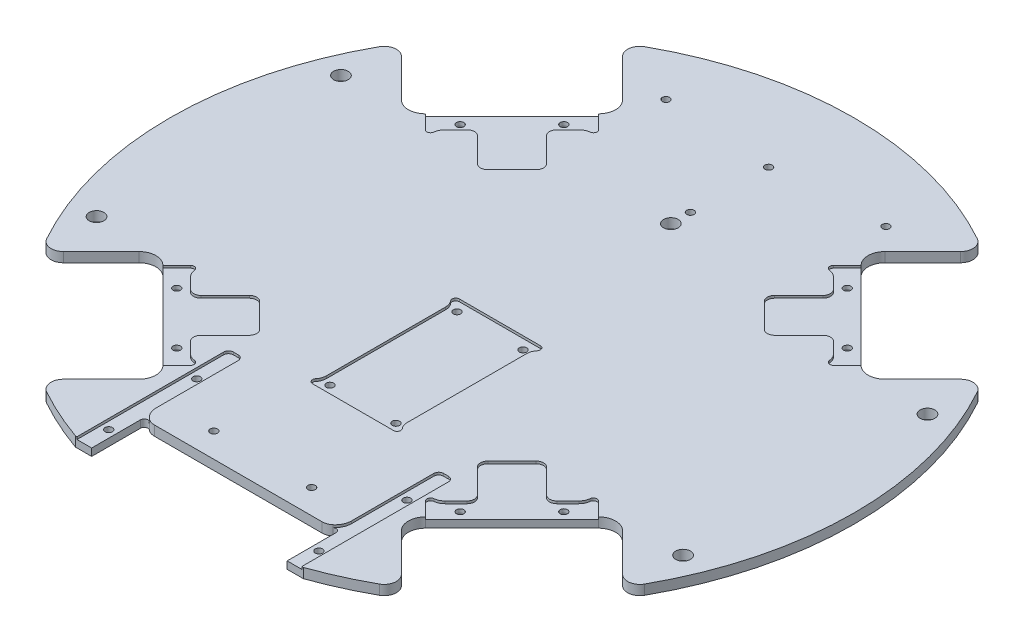
SolidWorks part; units mm, degrees
material "ABS PC"
ref_plane "Front Plane" through (0, 0, 0) normal (0, 0, 1) x (1, 0, 0)
ref_plane "Top Plane" through (0, 0, 0) normal (0, 1, 0) x (1, 0, 0)
ref_plane "Right Plane" through (0, 0, 0) normal (1, 0, 0) x (0, 0, -1)
sketch "Sketch1" plane through (0, 0, 0) normal (0, 1, 0) x (1, 0, 0)
  circle A0 centre (0, 0) radius 140
  dimension "D1" = 280
extrude "Boss-Extrude1" add sketch "Sketch1" along normal blind 4
sketch "Sketch7" plane through (0, 4, 0) normal (0, 1, 0) x (1, 0, 0)
  line L0 (-89.1308, -53.7048) -> (-53.7048, -89.1308)
  line L1 (-98.9596, -53.7048) -> (-121.6224, -76.3675)
  line L2 (-53.7048, -98.9596) -> (-76.3675, -121.6224)
  line L3 (-121.6224, -76.3675) -> (-76.3675, -121.6224)
  line L4 (0, 0) -> (-98.9949, -98.9949) construction
  line L7 (0, 0) -> (0, 130) construction
  circle A0 centre (0, 0) radius 140 construction
  arc A1 (-98.9596, -53.7048) -> (-89.1308, -53.7048) centre (-94.0452, -58.6192) cw
  arc A2 (-53.7048, -89.1308) -> (-53.7048, -98.9596) centre (-58.6192, -94.0452) cw
  dimension "D4" = 6.95
  dimension "D1" = 101
  dimension "D2" = 64
  dimension "D3" = 135
extrude "Cut-Extrude4" cut sketch "Sketch7" against normal up to next
sketch "Sketch8" plane through (0, 4, 0) normal (0, 1, 0) x (1, 0, 0)
  line L0 (-89.1308, -53.7048) -> (-53.7048, -89.1308)
  line L1 (-89.1308, -53.7048) -> (-83.474, -48.0479)
  line L2 (-53.7048, -89.1308) -> (-48.0479, -83.474)
  line L3 (-79.4765, -52.0454) -> (-52.0454, -79.4765)
  line L6 (-53.7048, -89.1308) -> (-89.1308, -53.7048) construction
  arc A0 (-83.474, -48.0479) -> (-80.9197, -48.9704) centre (-82.4133, -49.1086) cw
  arc A1 (-80.9197, -48.9704) -> (-79.4765, -52.0454) centre (-75.9409, -48.5099) ccw
  arc A2 (-48.0479, -83.474) -> (-48.9704, -80.9197) centre (-49.1086, -82.4133) ccw
  arc A3 (-48.9704, -80.9197) -> (-52.0454, -79.4765) centre (-48.5099, -75.9409) cw
  dimension "D2" = 1.5
  dimension "D3" = 5
  dimension "D4" = 1.5
  dimension "D5" = 5
  dimension "D1" = 8
extrude "Cut-Extrude5" cut sketch "Sketch8" against normal blind 1
sketch "Sketch14" plane through (0, 4, 0) normal (0, 1, 0) x (1, 0, 0)
  line L0 (-52.0454, -79.4765) -> (-79.4765, -52.0454) construction
  line L1 (-52.0454, -79.4765) -> (-79.4765, -52.0454) construction
  line L2 (-70.7107, -56.5685) -> (-60.8112, -46.669)
  line L3 (-56.5685, -70.7107) -> (-46.669, -60.8112)
  line L4 (-56.5685, -46.669) -> (-46.669, -56.5685)
  line L5 (-74.9533, -56.5685) -> (-56.5685, -74.9533)
  line L8 (-83.474, -48.0479) -> (-89.1308, -53.7048) construction
  arc A0 (-74.9533, -56.5685) -> (-70.7107, -56.5685) centre (-72.832, -54.4472) ccw
  arc A1 (-56.5685, -74.9533) -> (-56.5685, -70.7107) centre (-54.4472, -72.832) cw
  arc A2 (-60.8112, -46.669) -> (-56.5685, -46.669) centre (-58.6899, -48.7904) cw
  arc A3 (-46.669, -60.8112) -> (-46.669, -56.5685) centre (-48.7904, -58.6899) ccw
  dimension "D1" = 3
  dimension "D2" = 20
  dimension "D3" = 20
  dimension "D4" = 15.05
extrude "Cut-Extrude10" cut sketch "Sketch14" against normal up to surface (1 mm away) up to face at (-66.8825, 3, 66.8825)
sketch "Sketch9" plane through (0, 3, 0) normal (0, 1, 0) x (1, 0, 0)
  line L0 (-48.0479, -83.474) -> (-83.474, -48.0479) construction
  line L3 (-48.0479, -83.474) -> (-83.474, -48.0479) construction
  line L4 (-98.9596, -53.7048) -> (-119.0017, -73.7469) construction
  circle A0 centre (-79.196, -57.9828) radius 1.5
  circle A1 centre (-57.9828, -79.196) radius 1.5
  dimension "D4" = 3
  dimension "D1" = 4
  dimension "D2" = 30
  dimension "D3" = 17
  dimension "D5" = 4
extrude "Cut-Extrude6" cut sketch "Sketch9" against normal up to next
fillet "Fillet1" radius 5 2 edges at (-73.7469, 2, 119.0017) (-119.0017, 2, 73.7469)
pattern_circular "CirPattern1" count 4 over 360 about axis through (0, 4, 0) along (0, 1, 0) of "Cut-Extrude4", "Cut-Extrude6", "Fillet1", "Cut-Extrude5", "Cut-Extrude10"
sketch "Sketch2" plane through (0, 4, 0) normal (0, 1, 0) x (1, 0, 0)
  line L0 (-46.6476, -132) -> (-40, -132)
  line L1 (-40, -132) -> (-40, -112)
  line L2 (-34.3467, -112) -> (34.3467, -112)
  line L3 (40, -112) -> (40, -132)
  line L4 (40, -132) -> (46.6476, -132)
  line L5 (46.6476, -132) -> (46.6476, -140)
  line L6 (46.6476, -140) -> (-46.6476, -140)
  line L7 (-46.6476, -140) -> (-46.6476, -132)
  circle A0 centre (0, 0) radius 140 construction
  arc A1 (-40, -112) -> (-37.5415, -110.8462) centre (-38.5, -112) cw
  arc A2 (-34.3467, -112) -> (-37.5415, -110.8462) centre (-34.3467, -107) cw
  arc A3 (40, -112) -> (37.5415, -110.8462) centre (38.5, -112) ccw
  arc A4 (34.3467, -112) -> (37.5415, -110.8462) centre (34.3467, -107) ccw
  dimension "D5" = 1.5
  dimension "D6" = 5
  dimension "D1" = 8
  dimension "D2" = 20
  dimension "D3" = 80
  dimension "D4" = 6.6476
extrude "Cut-Extrude1" cut sketch "Sketch2" against normal up to next
sketch "Sketch3" plane through (0, 4, 0) normal (0, 1, 0) x (1, 0, 0)
  line L0 (-40, -132) -> (-46.6476, -132) construction
  line L1 (-40, -132) -> (-46, -132)
  line L2 (-40, -132) -> (-40, -72)
  line L3 (-42, -70) -> (-44, -70)
  line L4 (-46, -132) -> (-46, -72)
  line L5 (40, -132) -> (46, -132)
  line L6 (40, -132) -> (40, -72)
  line L7 (42, -70) -> (44, -70)
  line L8 (46, -132) -> (46, -72)
  line L12 (-40, -112) -> (-40, -132) construction
  line L13 (40, -132) -> (40, -112) construction
  arc A0 (40, -72) -> (42, -70) centre (42, -72) cw
  arc A1 (44, -70) -> (46, -72) centre (44, -72) cw
  arc A2 (-40, -72) -> (-42, -70) centre (-42, -72) ccw
  arc A3 (-44, -70) -> (-46, -72) centre (-44, -72) ccw
  dimension "D5" = 2
  dimension "D1" = 6
  dimension "D2" = 62
extrude "Cut-Extrude2" cut sketch "Sketch3" against normal blind 1
sketch "Sketch18" plane through (0, 4, 0) normal (0, 1, 0) x (1, 0, 0)
  line L0 (-40, -112) -> (-40, -72) construction
  line L1 (-40, -112) -> (-40, -72) construction
  line L3 (-40, -105.608) -> (-40, -112)
  line L4 (-40, -112) -> (-37.5415, -110.8462)
  line L5 (40, -72) -> (40, -112) construction
  line L6 (40, -105.608) -> (40, -112)
  line L7 (40, -112) -> (37.5415, -110.8462)
  arc A0 (-37.5415, -110.8462) -> (-40, -105.608) centre (-33.1904, -105.608) cw
  arc A2 (-37.5415, -110.8462) -> (-34.3467, -112) centre (-34.3467, -107) ccw construction
  arc A3 (37.5415, -110.8462) -> (40, -105.608) centre (33.1904, -105.608) ccw
  arc A4 (34.3467, -112) -> (37.5415, -110.8462) centre (34.3467, -107) ccw construction
extrude "Cut-Extrude14" cut sketch "Sketch18" against normal up to surface (1 mm away) up to face at (42.5714, 3, 94.1674)
fillet "Fillet3" radius 1.5 8 edges at (57.9828, 0, 80.696) (79.196, 0, 59.4828) (79.196, 0, -56.4828) (57.9828, 0, -77.696) (-57.9828, 0, -77.696) (-79.196, 0, -56.4828) (-57.9828, 0, 80.696) (-79.196, 0, 59.4828)
sketch "Sketch10" plane through (0, 4, 0) normal (0, 1, 0) x (1, 0, 0)
  circle A0 centre (-13.5, -61) radius 1.5
  circle A1 centre (13.5, -61) radius 1.5
  circle A2 centre (-13.5, -9) radius 1.5
  circle A3 centre (13.5, -9) radius 1.5
  dimension "D3" = 3
  dimension "D1" = 13.5
  dimension "D2" = 27
  dimension "D4" = 61
  dimension "D5" = 52
extrude "Cut-Extrude7" cut sketch "Sketch10" against normal up to next
sketch "Sketch11" plane through (0, 4, 0) normal (0, 1, 0) x (1, 0, 0)
  line L0 (34.3467, -112) -> (-34.3467, -112) construction
  circle A0 centre (-20, -102) radius 1.5
  circle A1 centre (20, -102) radius 1.5
  dimension "D1" = 3
  dimension "D2" = 40
  dimension "D3" = 10
  dimension "D4" = 20
extrude "Cut-Extrude8" cut sketch "Sketch11" against normal up to next
sketch "Sketch13" plane through (0, 4, 0) normal (0, 1, 0) x (1, 0, 0)
  line L0 (-46, -132) -> (-40, -132) construction
  line L4 (-40, -105.608) -> (-40, -72) construction
  line L5 (40, -72) -> (40, -105.608) construction
  circle A0 centre (-43, -86) radius 1.5
  circle A1 centre (-43, -122) radius 1.5
  circle A2 centre (43, -122) radius 1.5
  circle A3 centre (43, -86) radius 1.5
  dimension "D1" = 3
  dimension "D2" = 10
  dimension "D3" = 36
  dimension "D4" = 3
  dimension "D5" = 3
extrude "Cut-Extrude9" cut sketch "Sketch13" against normal up to next
sketch "Sketch15" plane through (0, 4, 0) normal (0, 1, 0) x (1, 0, 0)
  line L1 (-16.55, -4.95) -> (16.55, -4.95)
  line L2 (-16.55, -10.6033) -> (-16.55, -59.3967)
  line L3 (-16.55, -65.05) -> (16.55, -65.05)
  line L4 (16.55, -10.6033) -> (16.55, -59.3967)
  circle A0 centre (-13.5, -61) radius 1.5 construction
  circle A1 centre (-13.5, -9) radius 1.5 construction
  arc A2 (-16.55, -4.95) -> (-17.7038, -7.4085) centre (-16.55, -6.45) ccw
  arc A3 (-16.55, -10.6033) -> (-17.7038, -7.4085) centre (-21.55, -10.6033) ccw
  arc A4 (16.55, -4.95) -> (17.7038, -7.4085) centre (16.55, -6.45) cw
  arc A5 (17.7038, -7.4085) -> (16.55, -10.6033) centre (21.55, -10.6033) ccw
  arc A6 (-16.55, -65.05) -> (-17.7038, -62.5915) centre (-16.55, -63.55) cw
  arc A7 (-17.7038, -62.5915) -> (-16.55, -59.3967) centre (-21.55, -59.3967) ccw
  arc A8 (16.55, -65.05) -> (17.7038, -62.5915) centre (16.55, -63.55) ccw
  arc A9 (17.7038, -62.5915) -> (16.55, -59.3967) centre (21.55, -59.3967) cw
  dimension "D3" = 4.05
  dimension "D5" = 1.5
  dimension "D6" = 5
  dimension "D1" = 33.1
  dimension "D2" = 4.05
  dimension "D4" = 16.55
extrude "Cut-Extrude11" cut sketch "Sketch15" against normal blind 1
sketch "Sketch16" plane through (0, 4, 0) normal (0, 1, 0) x (1, 0, 0)
  circle A0 centre (0, 73) radius 1.5
  circle A1 centre (-45, 108) radius 1.5
  circle A2 centre (45, 108) radius 1.5
  circle A3 centre (0, 105) radius 1.5
  circle A4 centre (0, 65) radius 3
  dimension "D2" = 3
  dimension "D5" = 6
  dimension "D1" = 73
  dimension "D3" = 108
  dimension "D4" = 90
  dimension "D6" = 32
  dimension "D7" = 65
extrude "Cut-Extrude12" cut sketch "Sketch16" against normal up to next
sketch "Sketch17" plane through (0, 4, 0) normal (0, 1, 0) x (1, 0, 0)
  circle A0 centre (-120, 50) radius 3
  circle A1 centre (-120, -50) radius 3
  circle A2 centre (120, 50) radius 3
  circle A3 centre (120, -50) radius 3
  dimension "D1" = 6
  dimension "D2" = 50
  dimension "D3" = 50
  dimension "D4" = 120
  dimension "D5" = 120
extrude "Cut-Extrude13" cut sketch "Sketch17" against normal up to next
